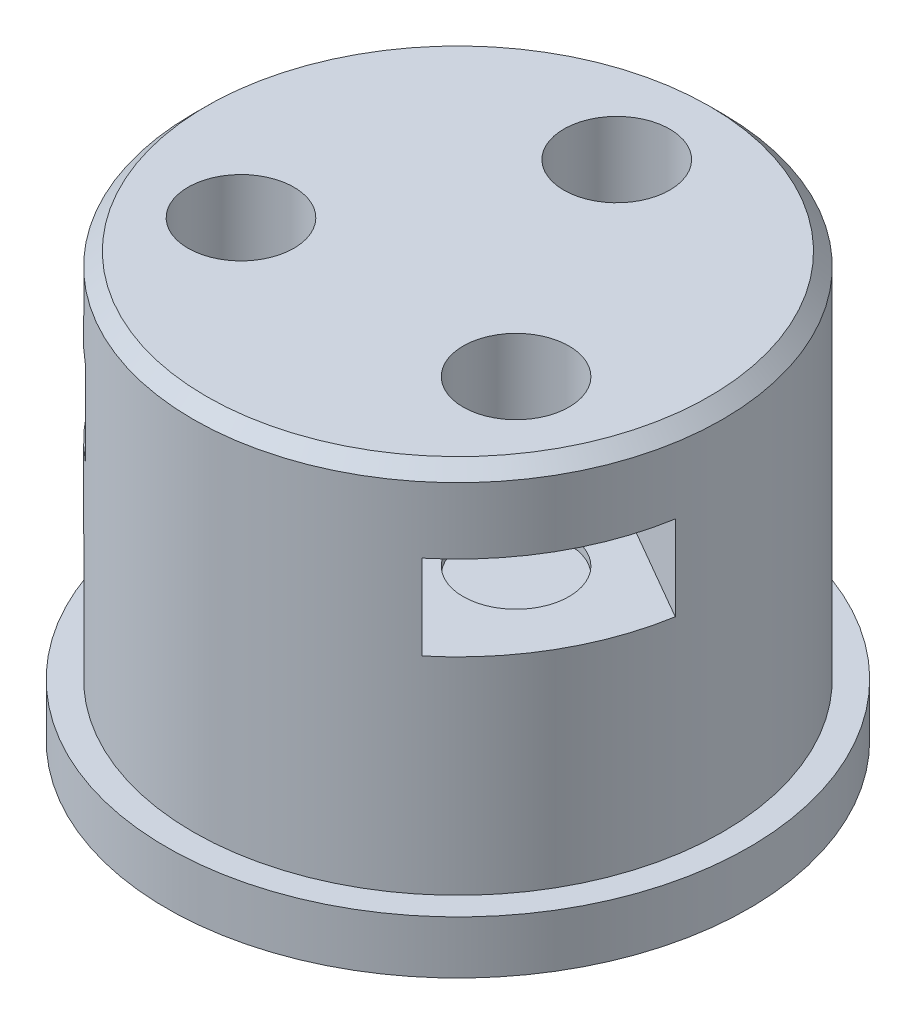
SolidWorks part; units mm, degrees
material "PLA"
ref_plane "Front Plane" through (0, 0, 0) normal (0, 0, 1) x (1, 0, 0)
ref_plane "Top Plane" through (0, 0, 0) normal (0, 1, 0) x (1, 0, 0)
ref_plane "Right Plane" through (0, 0, 0) normal (1, 0, 0) x (0, 0, -1)
sketch "Sketch1" plane through (0, 0, 0) normal (0, 1, 0) x (1, 0, 0)
  circle A0 centre (0, 0) radius 10
  circle A1 centre (0, 0) radius 8 construction
  dimension "D1" = 20
  dimension "D2" = 16
extrude "Boss-Extrude1" add sketch "Sketch1" along normal blind 16
sketch "Sketch2" plane through (0, 0, 0) normal (0, -1, 0) x (1, 0, 0)
  circle A0 centre (0, 0) radius 10 construction
  circle A1 centre (0, 0) radius 10
  circle A2 centre (0, 0) radius 11
extrude "Boss-Extrude2" add sketch "Sketch2" against normal blind 2
sketch "Sketch3" plane through (0, 0, 0) normal (0, -1, 0) x (1, 0, 0)
  circle A0 centre (0, 0) radius 8
  dimension "D1" = 16
extrude "Cut-Extrude1" cut sketch "Sketch3" against normal blind 6.5
sketch "Sketch4" plane through (0, 16, 0) normal (0, 1, 0) x (1, 0, 0)
  circle A0 centre (0, 0) radius 6 construction
  circle A1 centre (0, 6) radius 2
  circle A2 centre (5.1962, -3) radius 2
  circle A3 centre (-5.1962, -3) radius 2
  point P14 (0, 0)
  dimension "D1" = 12
  dimension "D2" = 4
  dimension "D3" = 3
extrude "Cut-Extrude2" cut sketch "Sketch4" against normal blind 6.5
sketch "Sketch5" plane through (0, 16, 0) normal (0, 1, 0) x (1, 0, 0)
  line L0 (-3.5, 8.0207) -> (-3.5, 9.3675)
  line L1 (0, 1.9585) -> (3.5, 3.9793)
  line L2 (3.5, 3.9793) -> (3.5, 8.0207)
  line L3 (3.5, 8.0207) -> (0, 10.0415)
  line L4 (0, 10.0415) -> (-3.5, 8.0207)
  line L5 (-3.5, 8.0207) -> (-3.5, 3.9793)
  line L6 (-3.5, 3.9793) -> (0, 1.9585)
  line L7 (3.5, 8.0207) -> (3.5, 9.3675)
  line L8 (8.6962, -0.9793) -> (9.8625, -1.6527)
  line L9 (8.6962, -0.9793) -> (5.1962, 1.0415)
  line L10 (8.6962, -5.0207) -> (8.6962, -0.9793)
  line L11 (5.1962, -7.0415) -> (8.6962, -5.0207)
  line L12 (5.1962, -7.0415) -> (6.3625, -7.7148)
  line L13 (1.6962, -5.0207) -> (5.1962, -7.0415)
  line L14 (1.6962, -0.9793) -> (1.6962, -5.0207)
  line L15 (5.1962, 1.0415) -> (1.6962, -0.9793)
  line L16 (-5.1962, -7.0415) -> (-6.3625, -7.7148)
  line L17 (-5.1962, -7.0415) -> (-1.6962, -5.0207)
  line L18 (-8.6962, -5.0207) -> (-5.1962, -7.0415)
  line L19 (-8.6962, -0.9793) -> (-8.6962, -5.0207)
  line L20 (-8.6962, -0.9793) -> (-9.8625, -1.6527)
  line L21 (-5.1962, 1.0415) -> (-8.6962, -0.9793)
  line L22 (-1.6962, -0.9793) -> (-5.1962, 1.0415)
  line L23 (-1.6962, -5.0207) -> (-1.6962, -0.9793)
  circle A0 centre (0, 6) radius 3.5 construction
  circle A1 centre (0, 0) radius 6 construction
  circle A3 centre (-5.1962, -3) radius 2
  circle A4 centre (-5.1962, -3) radius 2
  circle A5 centre (5.1962, -3) radius 2
  circle A6 centre (5.1962, -3) radius 2
  circle A7 centre (0, 6) radius 2
  circle A8 centre (0, 6) radius 2
  circle A9 centre (0, 0) radius 10 construction
  circle A10 centre (0, 0) radius 10
  point P50 (0, 0)
  circle M11 centre (0, 6) radius 2
  circle M12 centre (5.1962, -3) radius 2
  circle M13 centre (-5.1962, -3) radius 2
  circle M15 centre (0, 0) radius 10
  dimension "D5" = 7
  dimension "D4" = 0
  dimension "D6" = 3
extrude "Cut-Extrude3" cut sketch "Sketch5" against normal blind 3.2 from offset 3 contours L18 L16 M15 | L17 L23 L22 L21 L19 L18 M15 M13 | L19 L20 M15 | L5 L6 L1 L2 L3 L4 M15 M11 | L4 L0 M15 | L3 L7 M15 | L10 L8 M15 | L9 L15 L14 L13 L11 L10 M15 M12 | L11 L12 M15 region at (-2.2825, 16, -9.2115) region at (-1.7328, 16, -8.9179) region at (-9.1186, 16, 2.629) region at (2.2825, 16, -9.2115) region at (-6.8927, 16, 0.0615) region at (-6.8361, 16, 6.5825) region at (9.1186, 16, 2.629) region at (6.8361, 16, 6.5825) region at (8.5892, 16, 2.9583) offset against normal yes
sketch "Sketch6" plane through (0, 0, 0) normal (0, -1, 0) x (1, 0, 0)
  circle A0 centre (0, 0) radius 8
  circle A1 centre (0, 0) radius 7
  circle A2 centre (0, 0) radius 8 construction
extrude "Boss-Extrude3" add sketch "Sketch6" against normal up to surface (6.5 mm away) from offset 5 up to face at (0, 6.5, -8) offset against normal yes
chamfer "Chamfer1" distance 0.5 angle 45 1 edges at (0, 16, 10)
equation "\"Ns\" = 68"
equation "\"Np_b\" = 32"
equation "\"Np_s\" = 28"
equation "\"Nr_b\" = 132"
equation "\"module\" = 0.7"
equation "\"pressure_angle\" = 20.0"
equation "\"h_a\" = 0.7"
equation "\"h_f\" = 0.875"
equation "\"clr_tip_root\" = 0.17500000000000004"
equation "\"dp_r_b\" = 92.39999999999999"
equation "\"db_r_b\" = 86.82759816061792"
equation "\"fw_r_b\" = 59.79163091119555"
equation "\"alpha_r_b\" = 0.8539582918412556"
equation "\"beta_r_b\" = 3.0715529473188745"
equation "\"bearing_ID\" = 75"
equation "\"bearing_OD\" = 95"
equation "\"bearing_height\" = 10"
equation "\"clearance_planet\" = 1.5"
equation "\"case_dist\" = 6.5"
equation "\"Motor_case_OD_max\" = 131.3"
equation "\"case_mounting_PCD\" = 123.8"
equation "\"bearing mount thickness\" = 8"
equation "\"case_mounting_hole_dia\" = 3"
equation "\"output_mounting_PCD\" = 103"
equation "\"output_mounting_hole_dia\" = 4"
equation "\"clearance_case_mount_holes_shell_thickness\" = 1"
equation "\"motor_case_OD_base\" = 121.8"
equation "\"sec_carrier_thickness\" = 5"
equation "\"sun_coupler_hub_thickness\" = 4"
equation "\"clearance_sun_coupler_sec_carrier\" = 1.5"
equation "\"clearance_motor_and_case\" = 5"
equation "\"motor_OD\" = 106.8"
equation "\"Motor_case_thickness\" = 2.5"
equation "\"Motor_case_ID\" = 116.8"
equation "\"case_mounting_hole_shift\" = 1.0"
equation "\"output_mounting_nut_wrench_size\" = 7"
equation "\"output_mounting_nut_thickness\" = 3.2"
equation "\"case_mounting_hole_allen_socket_dia\" = 5.5"
equation "\"output_mounting_nut_depth\" = 3"
equation "\"case_mounting_bolt_depth\" = 4.5"
equation "\"ring_radial_thickness\" = 5"
equation "\"ring_OD_b\" = 102.39999999999999"
equation "\"ring_to_chamfer_clearance\" = 1.5"
equation "\"Motor_case_OD_base_to_chamfer\" = 5"
equation "\"pattern_offset_from_motor_case_OD_base\" = 3"
equation "\"pattern_bulge_dia\" = 3"
equation "\"pattern_num_bulge\" = 18"
equation "\"pattern_depth\" = 2"
equation "\"motor_height\" = 47.6"
equation "\"case_mounting_wrench_size\" = 5.5"
equation "\"case_mounting_nut_clearance\" = 2"
equation "\"base_plate_thickness\" = 4"
equation "\"case_mounting_nut_thickness\" = 2.4"
equation "\"case_mounting_surface_height\" = 4"
equation "\"motor_mount_hole_PCD\" = 40"
equation "\"motor_mount_hole_dia\" = 5"
equation "\"motor_mount_hole_num\" = 4"
equation "\"central_hole_offset_from_motor_mount_PCD\" = 5"
equation "\"wire_slot_dist_from_center\" = 45.5"
equation "\"wire_slot_length\" = 10"
equation "\"wire_slot_radius\" = 3"
equation "\"driver_upper_holes_dist_from_center\" = 29"
equation "\"driver_lower_holes_dist_from_center\" = 13"
equation "\"driver_side_holes_dist_from_center\" = 22.5"
equation "\"driver_mount_holes_dia\" = 3"
equation "\"driver_mount_inserts_OD\" = 4.8"
equation "\"driver_mount_thickness\" = 1.5"
equation "\"driver_mount_height\" = 6"
equation "\"air_flow_hole_offset\" = 3"
equation "\"pressure angle\" = 20.0"
equation "\"h_b\" = 0.875"
equation "\"fw_p_s\" = 43.04181208067841"
equation "\"num_planet\" = 4"
equation "\"planet_pin_bolt_dia\" = 5"
equation "\"planet_pin_socket_head_dia\" = 8.5"
equation "\"carrier_PCD\" = 70.0"
equation "\"planet_shaft_dia\" = 8"
equation "\"planet_shaft_step_offset\" = 1"
equation "\"carrier_trapezoidal_support_sun_offset\" = 5"
equation "\"carrier_trapezoidal_support_hole_PCD_offset_bearing_ID\" = 4"
equation "\"carrier_trapezoidal_support_hole_dia\" = 3"
equation "\"carrier_trapezoidal_support_hole_socket_head_dia\" = 5.5"
equation "\"carrier_bearing_step_width\" = 1.5"
equation "\"standard_clearance_1_5mm\" = 1.5"
equation "\"standard_fillet_1_5mm\" = 1.5"
equation "\"sun_shaft_bearing_OD\" = 16"
equation "\"sun_shaft_bearing_width\" = 5"
equation "\"standard_bearing_insertion_chamfer\" = 0.5"
equation "\"carrier_trapezoidal_support_hole_wrench_size\" = 5.5"
equation "\"planet_pin_bolt_wrench_size\" = 8"
equation "\"planet_bearing_OD\" = 12"
equation "\"planet_bearing_width\" = 3.5"
equation "\"planet_bore\" = 10"
equation "\"motor_output_hole_PCD\" = 23"
equation "\"motor_output_hole_dia\" = 4"
equation "\"motor_output_hole_num\" = 4"
equation "\"dp_s\" = 47.599999999999994"
equation "\"db_s\" = 44.72936874940923"
equation "\"fw_s_calc\" = 3.860660122911967"
equation "\"alpha_s\" = 0.8539582918412556"
equation "\"beta_s\" = 0.9391422398469005"
equation "\"dp_p_b\" = 22.4"
equation "\"db_p_b\" = 21.049114705604346"
equation "\"alpha_p_b\" = 0.8539582918412556"
equation "\"beta_p_b\" = 3.917083416317489"
equation "\"sun_shaft_bearing_ID\" = 8"
equation "\"sun_hub_dia\" = 30.0"
equation "\"sun_central_bolt_dia\" = 5"
equation "\"sun_central_bolt_socket_head_dia\" = 8.5"
equation "\"fw_s_used\" = 110.33344299187397"
equation "\"motor_output_hole_CSK_OD\" = 8"
equation "\"motor_output_hole_CSK_head_height\" = 2.0"
equation "\"bearing_retainer_thickness\" = 2"
equation "\"fw_p_b\" = 59.79163091119555"
equation "\"dp_p_s\" = 19.599999999999998"
equation "\"db_p_s\" = 18.417975367403802"
equation "\"alpha_p_s\" = 0.8539582918412592"
equation "\"beta_p_s\" = 4.7206548448889105"
equation "\"Nr_s\" = 128"
equation "\"clr_tip_root_s\" = 0.17500000000000004"
equation "\"dp_r_s\" = 89.6"
equation "\"db_r_s\" = 84.19645882241738"
equation "\"fw_r_s\" = 41.54181208067841"
equation "\"alpha_r_s\" = 0.8539582918412556"
equation "\"beta_r_s\" = 3.114166583682511"
equation "\"D1@Boss-Extrude1\"=\"bearing_height\" + \"carrier_thickness\" + \"carrier_small_ring_inner_bearing_flap\""
equation "\"D1@Cut-Extrude1\"=\"sun_shaft_bearing_width\" + \"standard_clearance_1_5mm\""
equation "\"D5@Sketch5\"=\"small_ring_output_wall_to_bearing_shaft_attachement_nut_wrench\""
equation "\"small_ring_case_thickness\" = 4"
equation "\"carrier_thickness\" = 4"
equation "\"small_ring_output_wall_thickness\" = 5"
equation "\"small_ring_output_wall_to_bearing_shaft_attachement_hole_dia\" = 4"
equation "\"small_ring_output_wall_to_bearing_shaft_attachement_hole_pcd\" = 12"
equation "\"small_ring_output_wall_to_bearing_shaft_attachement_hole_num\" = 3"
equation "\"small_ring_output_wall_to_bearing_shaft_attachement_hole_CSK_OD\" = 8"
equation "\"small_ring_output_wall_to_bearing_shaft_attachement_hole_CSK_head_height\" = 2.0"
equation "\"carrier_small_ring_inner_bearing_ID\" = 20"
equation "\"carrier_small_ring_inner_bearing_OD\" = 32"
equation "\"carrier_small_ring_inner_bearing_height\" = 7"
equation "\"D1@Sketch1\"=\"carrier_small_ring_inner_bearing_ID\""
equation "\"D2@Sketch1\"=\"sun_shaft_bearing_OD\""
equation "\"D1@Sketch2\"=\"standard_clearance_1_5mm\"*2/3"
equation "\"D1@Sketch3\"=\"sun_shaft_bearing_OD\""
equation "\"D1@Sketch4\"=\"small_ring_output_wall_to_bearing_shaft_attachement_hole_pcd\""
equation "\"D2@Sketch4\"=\"small_ring_output_wall_to_bearing_shaft_attachement_hole_dia\""
equation "\"D3@Sketch4\"=\"small_ring_output_wall_to_bearing_shaft_attachement_hole_num\""
equation "\"D6@Sketch5\"=\"small_ring_output_wall_to_bearing_shaft_attachement_hole_num\""
equation "\"D19@Cut-Extrude3\"=\"standard_clearance_1_5mm\"*2"
equation "\"D1@Sketch6\"=\"standard_clearance_1_5mm\"*2/3"
equation "\"D19@Boss-Extrude3\"=\"sun_shaft_bearing_width\""
equation "\"small_ring_output_wall_to_bearing_shaft_attachement_hole_depth\" = 6.5"
equation "\"small_ring_output_wall_to_bearing_shaft_attachement_nut_wrench\" = 7"
equation "\"small_ring_output_wall_to_bearing_shaft_attachement_nut_thickness\" = 3.2"
equation "\"carrier_small_ring_inner_bearing_flap\" = 2"
equation "\"D1@Boss-Extrude2\"=\"carrier_small_ring_inner_bearing_flap\""
equation "\"D1@Cut-Extrude2\"=\"small_ring_output_wall_to_bearing_shaft_attachement_hole_depth\""
equation "\"D1@Cut-Extrude3\"=\"small_ring_output_wall_to_bearing_shaft_attachement_nut_thickness\""
equation "\"D1@Chamfer1\"=\"standard_bearing_insertion_chamfer\""
